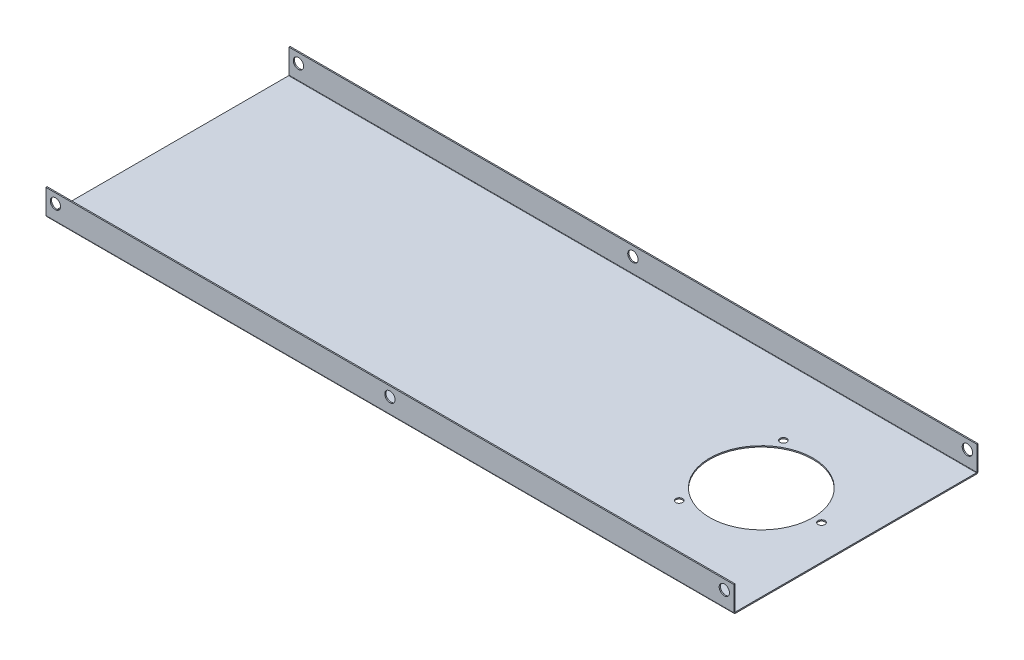
SolidWorks part; units mm, degrees
note: The reader was unsure of these and kept them because the rebuilt part matched: thickness of "基体-法兰1", "边线-法兰1", "钣金8", "钣金9", "钣金10", "钣金11", "钣金13"; flange length of "边线-法兰1".
ref_plane "前视基准面" through (0, 0, 0) normal (0, 0, 1) x (1, 0, 0)
ref_plane "上视基准面" through (0, 0, 0) normal (0, 1, 0) x (1, 0, 0)
ref_plane "右视基准面" through (0, 0, 0) normal (1, 0, 0) x (0, 0, -1)
sketch "草图1" plane through (0, 0, 0) normal (0, 1, 0) x (1, 0, 0)
  line L1 (-200, -71) -> (200, -71)
  line L2 (-200, -71) -> (-200, 71)
  line L3 (-200, 71) -> (200, 71)
  line L4 (200, -71) -> (200, 71)
  line L5 (-200, -71) -> (200, 71) construction
  line L6 (-200, 71) -> (200, -71) construction
  point P0 (0, 0)
  dimension "D1" = 142
  dimension "D2" = 400
base flange "基体-法兰1" sketch "草图1" thickness 0.7 reverse thickness direction no parameters "D1"=0.2
edge flange "边线-法兰1" sketch "草图15" flange profiles "草图15", "草图16" flange angle 90 flange length 15 flange position material inside bend radius 0.2 thickness 0.7 relief rectangular parameters "D6"=10, "D8"=1
sketch "草图15" plane through (0, 0, -71) normal (0, 0, -1) x (-1, 0, 0)
  line L2 (-200, 0) -> (-200, 14.3)
  line L3 (-200, 14.3) -> (200, 14.3)
  line L4 (200, 14.3) -> (200, 0)
  line L11 (-200, 0) -> (200, 0) construction
  line L12 (-200, 0) -> (200, 0)
sketch "草图16" plane through (0, 0, 71) normal (0, 0, 1) x (1, 0, 0)
  line L2 (-200, 0) -> (-200, 14.3)
  line L3 (-200, 14.3) -> (200, 14.3)
  line L4 (200, 14.3) -> (200, 0)
  line L7 (-200, 0) -> (200, 0) construction
  line L8 (-200, 0) -> (200, 0)
bend "边线折弯1" bend radius 0.2 bend angle 90 parameters "D5"=1
bend "边线折弯2" bend radius 0.2 bend angle 90 parameters "D5"=2
sketch "草图17" plane through (0, 0, -71) normal (0, 0, -1) x (-1, 0, 0)
  line L0 (200, 14.3) -> (-200, 14.3) construction
  line L1 (-200, 14.3) -> (-200, 0.2) construction
  line L2 (0, 14.3) -> (0, 0) construction
  circle A0 centre (-194.5, 8.8) radius 3
  circle A1 centre (0, 8.8) radius 3
  circle A2 centre (194.5, 8.8) radius 3
  dimension "D1" = 5.5
  dimension "D2" = 5.5
  dimension "D3" = 6
  dimension "D4" = 5.5
  dimension "D5" = 6
extrude "切除-拉伸1" cut sketch "草图17" against normal blind 10
sketch "草图18" plane through (0, 0, 71) normal (0, 0, 1) x (1, 0, 0)
  line L0 (200, 14.3) -> (-200, 14.3) construction
  line L1 (-200, 14.3) -> (-200, 0.2) construction
  line L2 (0, 14.3) -> (0, 0) construction
  circle A0 centre (-194.5, 8.8) radius 3
  circle A1 centre (0, 8.8) radius 3
  circle A2 centre (194.5, 8.8) radius 3
  dimension "D1" = 5.5
  dimension "D2" = 5.5
  dimension "D3" = 5.5
  dimension "D4" = 6
  dimension "D5" = 6
extrude "切除-拉伸2" cut sketch "草图18" against normal blind 10
sketch "草图19" plane through (0, -0.7, 0) normal (0, -1, 0) x (1, 0, 0)
  line L0 (200, 70.1) -> (200, -70.1) construction
  line L1 (-200, -70.1) -> (200, -70.1) construction
  line L2 (145, 0) -> (185, 0) construction
  line L3 (145, 0) -> (105, 0) construction
  line L4 (185, 0) -> (125, 34.641) construction
  line L5 (125, 34.641) -> (125, -34.641) construction
  line L6 (125, -34.641) -> (185, 0) construction
  line L7 (125, 34.641) -> (145, 0) construction
  line L8 (145, 0) -> (125, -34.641) construction
  line L9 (145, 0) -> (185, 0) construction
  circle A0 centre (145, 0) radius 40 construction
  circle A1 centre (145, 0) radius 20 construction
  circle A2 centre (145, 0) radius 30
  circle A3 centre (127.5, 30.3109) radius 2
  circle A4 centre (180, 0) radius 2
  circle A5 centre (127.5, -30.3109) radius 2
  dimension "D1" = 80
  dimension "D2" = 55
  dimension "D3" = 70.1
  dimension "D4" = 60
  dimension "D5" = 4
  dimension "D6" = 35
  dimension "D7" = 35
extrude "切除-拉伸4" cut sketch "草图19" against normal blind 10
sketch "折弯-线3" plane through (0, 0, 0) normal (0, 1, 0) x (1, 0, 0)
sketch "边界框3" plane through (0, 0, 0) normal (0, 1, 0) x (1, 0, 0)
sheet metal parameters "钣金8" thickness 0.7 parameters "D1"=0.2
flat pattern "平板型式8" [suppressed]
sketch "折弯-线4" plane through (0, 0, 0) normal (0, 1, 0) x (1, 0, 0)
sketch "边界框4" [suppressed] plane through (0, 0, 0) normal (0, 1, 0) x (1, 0, 0)
sheet metal parameters "钣金9" thickness 0.7 parameters "D1"=0.2, "D7"=0.01
flat pattern "平板型式8" [suppressed]
sketch "折弯-线4" plane through (0, 0, 0) normal (0, 1, 0) x (1, 0, 0)
sketch "边界框4" [suppressed] plane through (0, 0, 0) normal (0, 1, 0) x (1, 0, 0)
bend of the flat pattern "展平-<边线折弯1>1"
bend of the flat pattern "展平-<边线折弯2>1"
sheet metal parameters "钣金10" thickness 0.7 parameters "D1"=0.2, "D7"=0.01
flat pattern "平板型式8" [suppressed]
sketch "折弯-线4" plane through (0, 0, 0) normal (0, 1, 0) x (1, 0, 0)
sketch "边界框4" [suppressed] plane through (0, 0, 0) normal (0, 1, 0) x (1, 0, 0)
bend of the flat pattern "展平-<边线折弯1>1"
bend of the flat pattern "展平-<边线折弯2>1"
sheet metal parameters "钣金11" thickness 0.7 parameters "D1"=0.2, "D7"=0.01
flat pattern "平板型式8" [suppressed]
sketch "折弯-线4" plane through (0, 0, 0) normal (0, 1, 0) x (1, 0, 0)
sketch "边界框4" [suppressed] plane through (0, 0, 0) normal (0, 1, 0) x (1, 0, 0)
bend of the flat pattern "展平-<边线折弯1>1"
bend of the flat pattern "展平-<边线折弯2>1"
sheet metal parameters "钣金13" thickness 0.7 parameters "D1"=0.2, "D7"=0.01
flat pattern "平板型式8" [suppressed]
sketch "折弯-线4" plane through (0, 0, 0) normal (0, 1, 0) x (1, 0, 0)
sketch "边界框4" [suppressed] plane through (0, 0, 0) normal (0, 1, 0) x (1, 0, 0)
bend of the flat pattern "展平-<边线折弯1>1"
bend of the flat pattern "展平-<边线折弯2>1"
